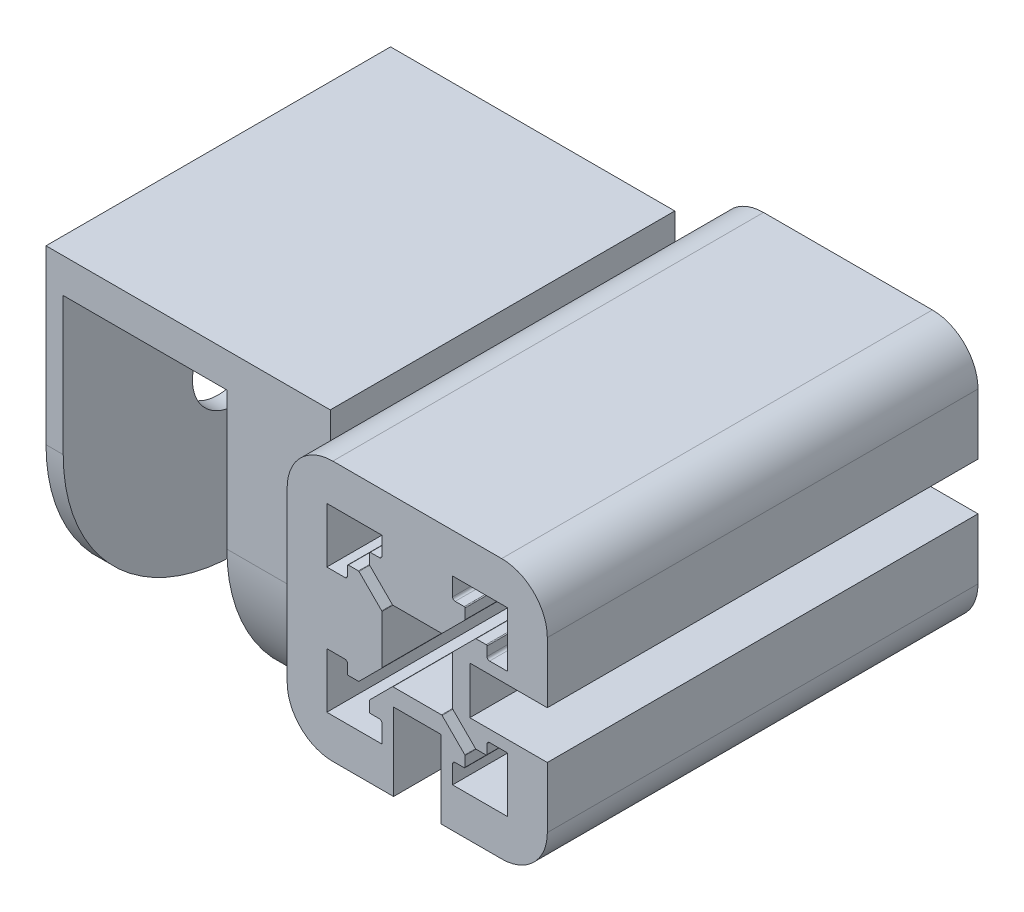
SolidWorks part; units mm, degrees
ref_plane "Ön Düzlem" through (0, 0, 0) normal (0, 0, 1) x (1, 0, 0)
ref_plane "Üst Düzlem" through (0, 0, 0) normal (0, 1, 0) x (1, 0, 0)
ref_plane "Sağ Düzlem" through (0, 0, 0) normal (1, 0, 0) x (0, 0, -1)
sketch "Çizim6" plane through (0, 0, 0) normal (0, 0, 1) x (1, 0, 0)
  line L5 (-115.3715, 18.9738) -> (-110.3715, 18.9738)
  line L6 (-115.3715, 13.4738) -> (-110.3715, 13.4738)
  line L64 (-135.0715, 20.3238) -> (-133.8715, 20.3238)
  line L65 (-133.5715, 20.6238) -> (-133.5715, 21.6738)
  line L66 (-133.4715, 21.7738) -> (-132.3044, 21.7738)
  line L67 (-132.2336, 21.7445) -> (-129.6008, 19.1116)
  line L68 (-129.5715, 19.0409) -> (-129.5715, 13.4066)
  line L69 (-132.2336, 10.7031) -> (-129.6008, 13.3359)
  line L70 (-133.4715, 10.6738) -> (-132.3044, 10.6738)
  line L71 (-133.5715, 11.8238) -> (-133.5715, 10.7738)
  line L72 (-135.0715, 12.1238) -> (-133.8715, 12.1238)
  line L79 (-129.5715, 6.6238) -> (-129.5715, 7.8238)
  line L80 (-129.8715, 8.1238) -> (-130.9215, 8.1238)
  line L81 (-131.0215, 8.2238) -> (-131.0215, 9.3909)
  line L82 (-130.9922, 9.4616) -> (-128.3594, 12.0945)
  line L83 (-128.2887, 12.1238) -> (-122.6544, 12.1238)
  line L84 (-119.9508, 9.4616) -> (-122.5836, 12.0945)
  line L85 (-119.9215, 8.2238) -> (-119.9215, 9.3909)
  line L86 (-121.0715, 8.1238) -> (-120.0215, 8.1238)
  line L87 (-121.3715, 6.6238) -> (-121.3715, 7.8238)
  line L94 (-115.8715, 12.1238) -> (-117.0715, 12.1238)
  line L95 (-117.3715, 11.8238) -> (-117.3715, 10.7738)
  line L96 (-117.4715, 10.6738) -> (-118.6387, 10.6738)
  line L97 (-118.7094, 10.7031) -> (-121.3422, 13.3359)
  line L98 (-121.3715, 13.4066) -> (-121.3715, 19.0409)
  line L99 (-118.7094, 21.7445) -> (-121.3422, 19.1116)
  line L100 (-117.4715, 21.7738) -> (-118.6387, 21.7738)
  line L101 (-117.3715, 20.6238) -> (-117.3715, 21.6738)
  line L102 (-115.8715, 20.3238) -> (-117.0715, 20.3238)
  line L109 (-121.3715, 25.8238) -> (-121.3715, 24.6238)
  line L110 (-121.0715, 24.3238) -> (-120.0215, 24.3238)
  line L111 (-119.9215, 24.2238) -> (-119.9215, 23.0566)
  line L112 (-119.9508, 22.9859) -> (-122.5836, 20.3531)
  line L113 (-122.6544, 20.3238) -> (-128.2887, 20.3238)
  line L114 (-130.9922, 22.9859) -> (-128.3594, 20.3531)
  line L115 (-131.0215, 24.2238) -> (-131.0215, 23.0566)
  line L116 (-129.8715, 24.3238) -> (-130.9215, 24.3238)
  line L117 (-129.5715, 25.8238) -> (-129.5715, 24.6238)
  line L122 (-119.3715, 18.9738) -> (-115.3715, 18.9738)
  line L123 (-119.3715, 13.4738) -> (-115.3715, 13.4738)
  line L126 (-119.3715, 18.9738) -> (-119.3715, 13.4738)
  line L128 (-122.7215, 10.1238) -> (-122.7215, 6.1238)
  line L129 (-122.7215, 10.1238) -> (-128.2215, 10.1238)
  line L130 (-128.2215, 10.1238) -> (-128.2215, 6.1238)
  line L142 (-135.0715, 20.3238) -> (-135.8715, 20.3238)
  line L143 (-135.0715, 12.1238) -> (-135.5715, 12.1238)
  line L144 (-129.5715, 6.6238) -> (-129.5715, 6.1238)
  line L145 (-129.5715, 25.8238) -> (-129.5715, 26.6238)
  line L146 (-121.3715, 25.8238) -> (-121.3715, 26.3238)
  line L147 (-115.8715, 20.3238) -> (-115.3715, 20.3238)
  line L148 (-115.8715, 12.1238) -> (-115.3715, 12.1238)
  line L149 (-121.3715, 6.6238) -> (-121.3715, 6.1238)
  line L150 (-135.2715, 31.3238) -> (-130.0215, 31.3238)
  line L151 (-130.0215, 31.3238) -> (-128.2215, 31.3238)
  line L152 (-125.4715, 31.3238) -> (-125.4715, 31.3238)
  line L153 (-125.4715, 31.3238) -> (-125.4715, 31.3238)
  line L154 (-125.4715, 31.3238) -> (-125.4715, 31.3238)
  line L155 (-120.9215, 31.3238) -> (-122.7215, 31.3238)
  line L156 (-120.9215, 31.3238) -> (-115.6715, 31.3238)
  line L157 (-110.3715, 20.7738) -> (-110.3715, 26.0238)
  line L158 (-110.3715, 20.7738) -> (-110.3715, 18.9738)
  line L159 (-110.3715, 16.2238) -> (-110.3715, 16.2238)
  line L160 (-110.3715, 16.2238) -> (-110.3715, 16.2238)
  line L161 (-110.3715, 16.2238) -> (-110.3715, 16.2238)
  line L162 (-110.3715, 11.6738) -> (-110.3715, 13.4738)
  line L163 (-110.3715, 6.4238) -> (-110.3715, 11.6738)
  line L164 (-120.9215, 1.1238) -> (-115.6715, 1.1238)
  line L165 (-120.9215, 1.1238) -> (-122.7215, 1.1238)
  line L166 (-125.4715, 1.1238) -> (-125.4715, 1.1238)
  line L167 (-125.4715, 1.1238) -> (-125.4715, 1.1238)
  line L168 (-125.4715, 1.1238) -> (-125.4715, 1.1238)
  line L169 (-130.0215, 1.1238) -> (-128.2215, 1.1238)
  line L170 (-135.2715, 1.1238) -> (-130.0215, 1.1238)
  line L171 (-140.5715, 6.4238) -> (-140.5715, 11.6738)
  line L172 (-140.5715, 11.6738) -> (-140.5715, 16.2238)
  line L173 (-140.5715, 16.2238) -> (-140.5715, 16.2238)
  line L174 (-140.5715, 16.2238) -> (-140.5715, 16.2238)
  line L175 (-140.5715, 16.2238) -> (-140.5715, 16.2238)
  line L176 (-140.5715, 20.7738) -> (-140.5715, 16.2238)
  line L177 (-140.5715, 20.7738) -> (-140.5715, 26.0238)
  line L178 (-135.5715, 20.7738) -> (-135.5715, 26.0238) construction
  line L179 (-135.2715, 26.3238) -> (-130.0215, 26.3238) construction
  line L180 (-115.3715, 20.7738) -> (-115.3715, 26.0238) construction
  line L181 (-120.9215, 26.3238) -> (-115.6715, 26.3238) construction
  line L182 (-115.3715, 20.7738) -> (-115.3715, 18.9738) construction
  line L183 (-115.3715, 6.4238) -> (-115.3715, 11.6738) construction
  line L184 (-120.9215, 6.1238) -> (-115.6715, 6.1238) construction
  line L185 (-115.3715, 11.6738) -> (-115.3715, 13.4738) construction
  line L186 (-120.9215, 6.1238) -> (-122.7215, 6.1238) construction
  line L187 (-120.9215, 26.3238) -> (-122.7215, 26.3238) construction
  line L188 (-130.0215, 26.3238) -> (-128.2215, 26.3238) construction
  line L189 (-135.5715, 20.7738) -> (-135.5715, 18.9738) construction
  line L190 (-135.5715, 11.6738) -> (-135.5715, 13.4738) construction
  line L191 (-135.5715, 6.4238) -> (-135.5715, 11.6738) construction
  line L192 (-135.2715, 6.1238) -> (-130.0215, 6.1238) construction
  line L193 (-130.0215, 6.1238) -> (-128.2215, 6.1238) construction
  line L194 (-122.7215, 6.1238) -> (-122.7215, 1.1238)
  line L195 (-128.2215, 6.1238) -> (-128.2215, 1.1238)
  line L196 (-135.8715, 20.3238) -> (-135.9715, 20.3238)
  line L197 (-135.9715, 20.2238) -> (-135.9715, 26.7238) construction
  line L198 (-122.7215, 31.3238) -> (-128.2215, 31.3238)
  line L204 (-110.3715, 20.7738) -> (-110.3715, 16.2238) construction
  line L205 (-110.3715, 11.6738) -> (-110.3715, 16.2238) construction
  line L206 (-120.9215, 31.3238) -> (-125.4715, 31.3238) construction
  line L207 (-130.0215, 31.3238) -> (-125.4715, 31.3238) construction
  line L208 (-120.9215, 1.1238) -> (-125.4715, 1.1238) construction
  line L209 (-130.0215, 1.1238) -> (-125.4715, 1.1238) construction
  line L210 (-131.5715, 13.4738) -> (-135.5715, 13.4738) [skipped]
  line L211 (-131.5715, 13.4738) -> (-135.5715, 13.4738) construction
  line L212 (-131.5715, 13.4738) -> (-131.5715, 18.9738) [skipped]
  line L213 (-131.5715, 13.4738) -> (-131.5715, 18.9738) construction
  line L214 (-131.5715, 18.9738) -> (-135.5715, 18.9738) [skipped]
  line L215 (-131.5715, 18.9738) -> (-135.5715, 18.9738) construction
  line L216 (-129.5715, 26.6238) -> (-129.5715, 26.7238)
  line L217 (-135.9715, 26.7238) -> (-129.4715, 26.7238) construction
  line L218 (-114.9715, 26.7238) -> (-114.9715, 20.3238)
  line L219 (-121.3715, 26.7238) -> (-114.9715, 26.7238)
  line L220 (-114.9715, 5.7238) -> (-121.3715, 5.7238)
  line L221 (-114.9715, 12.1238) -> (-114.9715, 5.7238)
  line L222 (-135.9715, 5.7238) -> (-135.9715, 12.1238)
  line L223 (-129.5715, 5.7238) -> (-135.9715, 5.7238)
  line L224 (-121.3715, 6.1238) -> (-121.3715, 5.7238)
  line L225 (-115.3715, 12.1238) -> (-114.9715, 12.1238)
  line L226 (-129.5715, 6.1238) -> (-129.5715, 5.7238)
  line L227 (-135.9715, 20.3238) -> (-135.9715, 26.7238)
  line L228 (-135.9715, 26.7238) -> (-129.5715, 26.7238)
  line L229 (-135.5715, 12.1238) -> (-135.9715, 12.1238)
  line L230 (-121.3715, 26.3238) -> (-121.3715, 26.7238)
  line L231 (-115.3715, 20.3238) -> (-114.9715, 20.3238)
  line L240 (-121.4715, 25.8238) -> (-121.4715, 26.3238) construction
  line L241 (-121.4715, 25.8238) -> (-121.4715, 24.6238) construction
  line L242 (-121.0715, 24.2238) -> (-120.0215, 24.2238) construction
  line L243 (-120.0215, 24.2238) -> (-120.0215, 23.0566) construction
  line L244 (-120.0215, 23.0566) -> (-122.6544, 20.4238) construction
  line L245 (-122.6544, 20.4238) -> (-128.2887, 20.4238) construction
  line L246 (-130.9215, 23.0566) -> (-128.2887, 20.4238) construction
  line L247 (-130.9215, 24.2238) -> (-130.9215, 23.0566) construction
  line L248 (-129.8715, 24.2238) -> (-130.9215, 24.2238) construction
  line L249 (-129.4715, 25.8238) -> (-129.4715, 24.6238) construction
  line L250 (-129.4715, 25.8238) -> (-129.4715, 26.7238) construction
  line L251 (-135.8715, 26.6238) -> (-129.5715, 26.6238) construction
  line L252 (-135.8715, 20.3238) -> (-135.8715, 26.6238) construction
  line L253 (-135.0715, 20.2238) -> (-135.9715, 20.2238) construction
  line L254 (-135.0715, 20.2238) -> (-133.8715, 20.2238) construction
  line L255 (-133.4715, 20.6238) -> (-133.4715, 21.6738) construction
  line L256 (-133.4715, 21.6738) -> (-132.3044, 21.6738) construction
  line L257 (-132.3044, 21.6738) -> (-129.6715, 19.0409) construction
  line L258 (-129.6715, 19.0409) -> (-129.6715, 13.4066) construction
  line L259 (-132.3044, 10.7738) -> (-129.6715, 13.4066) construction
  line L260 (-133.4715, 10.7738) -> (-132.3044, 10.7738) construction
  line L261 (-133.4715, 11.8238) -> (-133.4715, 10.7738) construction
  line L262 (-135.0715, 12.2238) -> (-133.8715, 12.2238) construction
  line L263 (-135.0715, 12.2238) -> (-135.5715, 12.2238) construction
  line L264 (-128.2215, 22.3238) -> (-128.2215, 26.3238) [skipped]
  line L265 (-128.2215, 22.3238) -> (-128.2215, 26.3238) construction
  line L266 (-128.2215, 22.3238) -> (-122.7215, 22.3238) [skipped]
  line L267 (-128.2215, 22.3238) -> (-122.7215, 22.3238) construction
  line L268 (-122.7215, 22.3238) -> (-122.7215, 26.3238) [skipped]
  line L269 (-122.7215, 22.3238) -> (-122.7215, 26.3238) construction
  arc A46 (-133.8715, 20.3238) -> (-133.5715, 20.6238) centre (-133.8715, 20.6238) ccw
  arc A47 (-133.5715, 21.6738) -> (-133.4715, 21.7738) centre (-133.4715, 21.6738) cw
  arc A48 (-132.2336, 21.7445) -> (-132.3044, 21.7738) centre (-132.3044, 21.6738) ccw
  arc A49 (-129.5715, 19.0409) -> (-129.6008, 19.1116) centre (-129.6715, 19.0409) ccw
  arc A50 (-129.5715, 13.4066) -> (-129.6008, 13.3359) centre (-129.6715, 13.4066) cw
  arc A51 (-132.2336, 10.7031) -> (-132.3044, 10.6738) centre (-132.3044, 10.7738) cw
  arc A52 (-133.4715, 10.6738) -> (-133.5715, 10.7738) centre (-133.4715, 10.7738) cw
  arc A53 (-133.5715, 11.8238) -> (-133.8715, 12.1238) centre (-133.8715, 11.8238) ccw
  arc A57 (-129.5715, 7.8238) -> (-129.8715, 8.1238) centre (-129.8715, 7.8238) ccw
  arc A58 (-130.9215, 8.1238) -> (-131.0215, 8.2238) centre (-130.9215, 8.2238) cw
  arc A59 (-130.9922, 9.4616) -> (-131.0215, 9.3909) centre (-130.9215, 9.3909) ccw
  arc A60 (-128.2887, 12.1238) -> (-128.3594, 12.0945) centre (-128.2887, 12.0238) ccw
  arc A61 (-122.6544, 12.1238) -> (-122.5836, 12.0945) centre (-122.6544, 12.0238) cw
  arc A62 (-119.9508, 9.4616) -> (-119.9215, 9.3909) centre (-120.0215, 9.3909) cw
  arc A63 (-119.9215, 8.2238) -> (-120.0215, 8.1238) centre (-120.0215, 8.2238) cw
  arc A64 (-121.0715, 8.1238) -> (-121.3715, 7.8238) centre (-121.0715, 7.8238) ccw
  arc A68 (-117.0715, 12.1238) -> (-117.3715, 11.8238) centre (-117.0715, 11.8238) ccw
  arc A69 (-117.3715, 10.7738) -> (-117.4715, 10.6738) centre (-117.4715, 10.7738) cw
  arc A70 (-118.7094, 10.7031) -> (-118.6387, 10.6738) centre (-118.6387, 10.7738) ccw
  arc A71 (-121.3715, 13.4066) -> (-121.3422, 13.3359) centre (-121.2715, 13.4066) ccw
  arc A72 (-121.3715, 19.0409) -> (-121.3422, 19.1116) centre (-121.2715, 19.0409) cw
  arc A73 (-118.7094, 21.7445) -> (-118.6387, 21.7738) centre (-118.6387, 21.6738) cw
  arc A74 (-117.4715, 21.7738) -> (-117.3715, 21.6738) centre (-117.4715, 21.6738) cw
  arc A75 (-117.3715, 20.6238) -> (-117.0715, 20.3238) centre (-117.0715, 20.6238) ccw
  arc A79 (-121.3715, 24.6238) -> (-121.0715, 24.3238) centre (-121.0715, 24.6238) ccw
  arc A80 (-120.0215, 24.3238) -> (-119.9215, 24.2238) centre (-120.0215, 24.2238) cw
  arc A81 (-119.9508, 22.9859) -> (-119.9215, 23.0566) centre (-120.0215, 23.0566) ccw
  arc A82 (-122.6544, 20.3238) -> (-122.5836, 20.3531) centre (-122.6544, 20.4238) ccw
  arc A83 (-128.2887, 20.3238) -> (-128.3594, 20.3531) centre (-128.2887, 20.4238) cw
  arc A84 (-130.9922, 22.9859) -> (-131.0215, 23.0566) centre (-130.9215, 23.0566) cw
  arc A85 (-131.0215, 24.2238) -> (-130.9215, 24.3238) centre (-130.9215, 24.2238) cw
  arc A86 (-129.8715, 24.3238) -> (-129.5715, 24.6238) centre (-129.8715, 24.6238) ccw
  arc A89 (-110.3715, 26.0238) -> (-115.6715, 31.3238) centre (-115.6715, 26.0238) ccw
  arc A90 (-115.6715, 1.1238) -> (-110.3715, 6.4238) centre (-115.6715, 6.4238) ccw
  arc A91 (-135.2715, 1.1238) -> (-140.5715, 6.4238) centre (-135.2715, 6.4238) cw
  arc A92 (-140.5715, 26.0238) -> (-135.2715, 31.3238) centre (-135.2715, 26.0238) cw
  arc A93 (-135.5715, 26.0238) -> (-135.2715, 26.3238) centre (-135.2715, 26.0238) cw construction
  arc A94 (-115.3715, 26.0238) -> (-115.6715, 26.3238) centre (-115.6715, 26.0238) ccw construction
  arc A95 (-115.6715, 6.1238) -> (-115.3715, 6.4238) centre (-115.6715, 6.4238) ccw construction
  arc A96 (-135.2715, 6.1238) -> (-135.5715, 6.4238) centre (-135.2715, 6.4238) cw construction
  arc A98 (-133.4715, 10.7738) -> (-133.4715, 10.7738) centre (-133.4715, 10.7738) cw
  arc A99 (-132.3044, 10.7738) -> (-132.3044, 10.7738) centre (-132.3044, 10.7738) cw
  arc A100 (-129.6715, 13.4066) -> (-129.6715, 13.4066) centre (-129.6715, 13.4066) cw
  arc A101 (-129.6715, 19.0409) -> (-129.6715, 19.0409) centre (-129.6715, 19.0409) ccw
  arc A102 (-132.3044, 21.6738) -> (-132.3044, 21.6738) centre (-132.3044, 21.6738) ccw
  arc A103 (-133.4715, 21.6738) -> (-133.4715, 21.6738) centre (-133.4715, 21.6738) cw
  arc A106 (-130.9215, 24.2238) -> (-130.9215, 24.2238) centre (-130.9215, 24.2238) cw
  arc A107 (-130.9215, 23.0566) -> (-130.9215, 23.0566) centre (-130.9215, 23.0566) cw
  arc A108 (-128.2887, 20.4238) -> (-128.2887, 20.4238) centre (-128.2887, 20.4238) cw
  arc A109 (-122.6544, 20.4238) -> (-122.6544, 20.4238) centre (-122.6544, 20.4238) ccw
  arc A110 (-120.0215, 23.0566) -> (-120.0215, 23.0566) centre (-120.0215, 23.0566) ccw
  arc A111 (-120.0215, 24.2238) -> (-120.0215, 24.2238) centre (-120.0215, 24.2238) cw
  arc A113 (-121.4715, 24.6238) -> (-121.0715, 24.2238) centre (-121.0715, 24.6238) ccw construction
  arc A114 (-129.8715, 24.2238) -> (-129.4715, 24.6238) centre (-129.8715, 24.6238) ccw construction
  arc A115 (-133.8715, 20.2238) -> (-133.4715, 20.6238) centre (-133.8715, 20.6238) ccw construction
  arc A116 (-133.4715, 11.8238) -> (-133.8715, 12.2238) centre (-133.8715, 11.8238) ccw construction
  point P0 (-125.4715, 16.2238)
  point P123 (-125.4715, 16.2238)
  point P329 (-125.4715, 16.2238)
  dimension "D6" = 4
  dimension "D2" = 0.1
  dimension "D3" = 5
  dimension "D4" = 2.4
  dimension "D5" = 2.4
  dimension "D14" = 4
extrude "Yükseklik-Ekstrüzyon3" add sketch "Çizim6" along normal mid plane 50 contours A92 L177 L176 L172 L171 A91 L170 L169 L195 L130 L129 L128 L194 L165 L164 A90 L163 L162 L6 L123 L126 L122 L5 L158 L157 A89 L156 L155 L151 L150 A86 L116 A85 L115 A84 L114 A83 L113 A82 L112 A81 L111 A80 L110 A79 region at (-117.3715, 19.4009, 0)
sketch "Çizim8" plane through (-140.5715, 0, 0) normal (-1, 0, 0) x (0, 0, 1)
  line L0 (-28.2908, 27.6575) -> (28.2908, -5.01) construction
  line L1 (0, 11.3238) -> (61.9444, 11.3238)
  line L2 (0, 48.762) -> (0, 11.3238)
  line L3 (0, 11.3238) -> (0, -31.4872)
  line L4 (0, 11.3238) -> (-26.7349, 11.3238)
  line L5 (-20, 31.3238) -> (20, 31.3238)
  line L6 (-20, 31.3238) -> (-20, -8.6762)
  line L7 (20, 31.3238) -> (20, -8.6762)
  line L8 (-20, -8.6762) -> (20, -8.6762)
  line L9 (-20, 31.3238) -> (20, -8.6762) construction
  line L10 (20, 31.3238) -> (-20, -8.6762) construction
  line L11 (25, 31.3238) -> (-25, 31.3238) construction
  line L12 (20, 11.3238) -> (51.6727, 11.3238)
  line M12 (-25, 6.4238) -> (25, 6.4238)
  line M14 (25, 26.0238) -> (-25, 26.0238)
  dimension "D1" = 60
  dimension "D2" = 90
  dimension "D3" = 40
  dimension "D4" = 40
extrude "Yükseklik-Ekstrüzyon4" add sketch "Çizim8" along normal blind 33 contours L5 L6 L2 M14 | L7 L5 L2 M14 | L7 L2 L1 M14 | L6 L4 L2 M14 | L6 L8 L3 M12 | L4 L6 L3 M12 | L7 L1 L3 M12 | L3 L8 L7 M12 | L5 L6 L8 L7 region at (-140.5715, 18.6738, 10) region at (-140.5715, 18.6738, -10) region at (-140.5715, 8.8738, 10) region at (-140.5715, 8.8738, -10) region at (-140.5715, 28.6738, -10) region at (-140.5715, 28.6738, 10) region at (-140.5715, -1.1262, 10) region at (-140.5715, -1.1262, -10)
sketch "Çizim9" plane through (0, -8.6762, 0) normal (0, -1, 0) x (1, 0, 0)
  line L6 (-171.5715, 18) -> (-171.5715, -18)
  line L7 (-171.5715, -18) -> (-152.5715, -18)
  line L9 (-152.5715, 18) -> (-171.5715, 18)
  line L10 (-140.5715, -20) -> (-140.5715, 20)
  line L11 (-140.5715, 20) -> (-173.5715, 20)
  line L18 (-173.5715, 20) -> (-173.5715, -20)
  line L19 (-173.5715, -20) -> (-140.5715, -20)
  line L20 (-140.5715, -20) -> (-140.5715, 20)
  line L22 (-173.5715, 20) -> (-173.5715, -20)
  line L23 (-173.5715, -20) -> (-140.5715, -20)
  line L24 (-152.5715, -18) -> (-152.5715, 18)
  line L25 (-171.5715, -18) -> (-142.5715, -18) construction
  line L26 (-142.5715, 18) -> (-171.5715, 18) construction
  line L28 (-140.5715, 20) -> (-173.5715, 20) construction
  line L30 (-140.5715, 20) -> (-173.5715, 20)
  line L31 (-142.5715, -18) -> (-142.5715, 18) construction
  dimension "D3" = 12
  dimension "D1" = 0
  dimension "D2" = 2
extrude "Kes-Ekstrüzyon1" cut sketch "Çizim9" against normal blind 36 contours L7 L24 L9 L6
sketch "Çizim11" plane through (-173.5715, 0, 0) normal (-1, 0, 0) x (0, 0, 1)
  line L0 (20, 31.3238) -> (20, -8.6762) construction
  line L1 (20, 11.3238) -> (-20, 11.3238) construction
  line L2 (-20, 31.3238) -> (-20, -8.6762) construction
  circle A0 centre (0, 11.3238) radius 5
  dimension "D1" = 10
extrude "Kes-Ekstrüzyon3" cut sketch "Çizim11" against normal blind 10 contours A0
sketch "Çizim12" plane through (0, 0, -20) normal (0, 0, -1) x (-1, 0, 0)
  line L2 (171.5715, -8.6762) -> (171.5715, 27.3238)
  line L3 (171.5715, 27.3238) -> (152.5715, 27.3238)
  line L4 (140.5715, 31.3238) -> (140.5715, 26.0238)
  line L5 (173.5715, 31.3238) -> (140.5715, 31.3238)
  line L6 (173.5715, 31.3238) -> (140.5715, 31.3238) construction
  line L7 (173.5715, 31.3238) -> (173.5715, -8.6762) construction
  line L12 (173.5715, -8.6762) -> (140.5715, -8.6762) construction
  line L13 (152.5715, 27.3238) -> (152.5715, -8.6762)
  line L16 (140.5715, -8.6762) -> (173.5715, -8.6762)
  line L17 (152.5715, -8.6762) -> (171.5715, -8.6762)
  line L18 (173.5715, -8.6762) -> (173.5715, 31.3238)
  line L19 (140.5715, 26.0238) -> (140.5715, 6.4238)
  line L20 (140.5715, 26.0238) -> (140.5715, 6.4238)
  line L21 (140.5715, 6.4238) -> (140.5715, -8.6762)
  line L22 (140.5715, 6.4238) -> (140.5715, -8.6762)
  line M9 (140.5715, -8.6762) -> (173.5715, -8.6762)
  dimension "D2" = 4
  dimension "D3" = 2
  dimension "D4" = 12
  dimension "D1" = 0
extrude "Kes-Ekstrüzyon4" cut sketch "Çizim12" against normal blind 93 contours L2 L3 M9 region at (-162.0715, 9.3238, -20)
sketch "Çizim13" plane through (-173.5715, 0, 0) normal (-1, 0, 0) x (0, 0, 1)
  line L4 (-20, -8.6762) -> (20, -8.6762)
  line L5 (20, -8.6762) -> (20, 31.3238)
  line L6 (20, 31.3238) -> (-20, 31.3238)
  line L7 (-20, 31.3238) -> (-20, -8.6762)
  line L8 (-20, -8.6762) -> (20, -8.6762)
  line L9 (20, -8.6762) -> (20, 11.3238)
  line L10 (20, 31.3238) -> (-20, 31.3238)
  line L11 (-20, 11.3238) -> (-20, -8.6762)
  arc A0 (-20, 11.3238) -> (20, 11.3238) centre (0, 11.3238) ccw
  line M7 (-20, -8.6762) -> (20, -8.6762)
  line M8 (20, -8.6762) -> (20, 31.3238)
  line M10 (-20, 31.3238) -> (-20, -8.6762)
  dimension "D1" = 0
extrude "Kes-Ekstrüzyon5" cut sketch "Çizim13" against normal up to surface (33 mm away) and the other way blind 2 contours A0 M10 M7 | A0 L8 M8 region at (-173.5715, -4.2089, -15.5326) region at (-173.5715, -4.2089, 15.5326) up to face at (-140.5715, -1.1262, 0)
